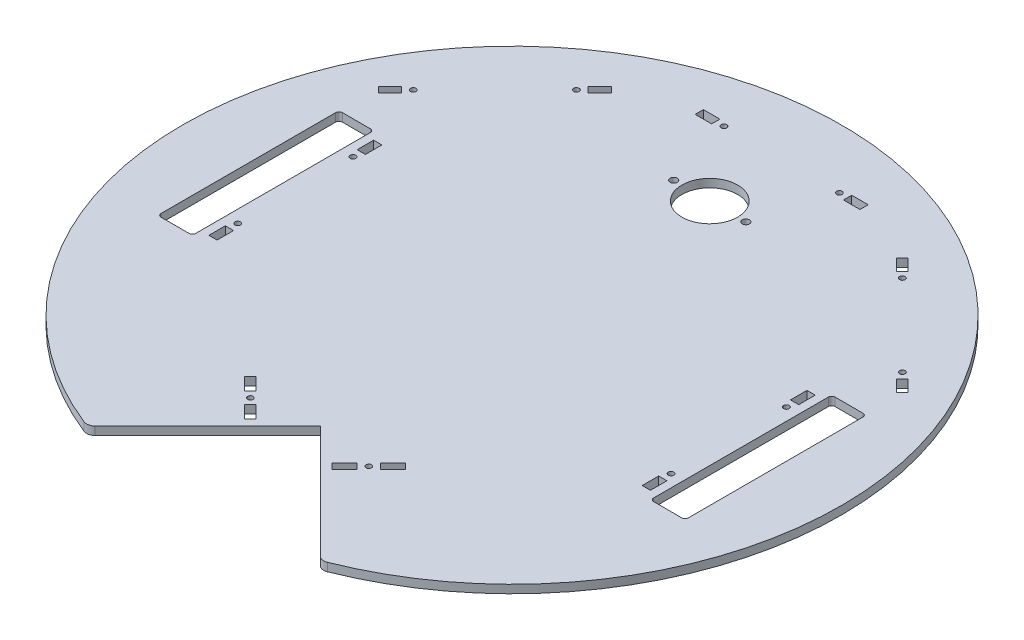
SolidWorks part; units mm, degrees
ref_plane "Front Plane" through (0, 0, 0) normal (0, 0, 1) x (1, 0, 0)
ref_plane "Top Plane" through (0, 0, 0) normal (0, 1, 0) x (1, 0, 0)
ref_plane "Right Plane" through (0, 0, 0) normal (1, 0, 0) x (0, 0, -1)
sketch "Sketch1" plane through (0, 0, 0) normal (0, 1, 0) x (1, 0, 0)
  circle A0 centre (0, 0) radius 254
  dimension "D1" = 508
extrude "Boss-Extrude1" add sketch "Sketch1" along normal blind 6.35
sketch "Sketch2" plane through (0, 6.35, 0) normal (0, 1, 0) x (1, 0, 0)
  line L0 (0, -147.7927) -> (-89.8026, -237.5952)
  line L1 (0, -36.2008) -> (0, -54.9716) construction
  line L2 (0, -147.7927) -> (89.8026, -237.5952)
  circle A0 centre (0, 0) radius 254 construction
  arc A1 (-89.8026, -237.5952) -> (89.8026, -237.5952) centre (0, 0) ccw
  dimension "D1" = 127
  dimension "D2" = 45
extrude "Cut-Extrude2" cut sketch "Sketch2" against normal through all
sketch "Sketch3" plane through (0, 6.35, 0) normal (0, 1, 0) x (1, 0, 0)
  line L0 (-31.4309, -170.2433) -> (-26.9408, -165.7532)
  line L1 (-31.4309, -170.2433) -> (-40.4112, -161.2631)
  line L2 (-26.9408, -165.7532) -> (-35.921, -156.7729)
  line L3 (-40.4112, -161.2631) -> (-35.921, -156.7729)
  line L4 (0, -147.7927) -> (-89.8026, -237.5952) construction
  line L5 (89.8026, -237.5952) -> (0, -147.7927) construction
  line L6 (-38.1661, -159.018) -> (-41.2194, -155.9647) construction
  circle A0 centre (-41.2194, -155.9647) radius 2.159
  dimension "D5" = 4.318
  dimension "D1" = 6.35
  dimension "D2" = 12.7
  dimension "D3" = 31.75
  dimension "D4" = 6.35
  dimension "D6" = 4.318
extrude "Cut-Extrude3" [suppressed] cut sketch "Sketch3" against normal through all
mirror "Mirror1" [suppressed] about plane through (0, 0, 0) normal (1, 0, 0)
sketch "Sketch4" plane through (0, 6.35, 0) normal (0, 1, 0) x (1, 0, 0)
  line L0 (0, 54.2551) -> (0, 121.7464) construction
  line L1 (-200.66, 69.85) -> (-179.07, 69.85)
  line L2 (-203.2, 67.31) -> (-203.2, -67.31)
  line L3 (-200.66, -69.85) -> (-179.07, -69.85)
  line L4 (-176.53, 67.31) -> (-176.53, -67.31)
  line L5 (-17.8666, 0) -> (24.1783, 0) construction
  line L6 (-254, -69.5481) -> (-254, -224.3367) construction
  arc A0 (-200.66, -69.85) -> (-203.2, -67.31) centre (-200.66, -67.31) cw
  arc A1 (-179.07, -69.85) -> (-176.53, -67.31) centre (-179.07, -67.31) ccw
  arc A2 (-176.53, 67.31) -> (-179.07, 69.85) centre (-179.07, 67.31) ccw
  arc A3 (-200.66, 69.85) -> (-203.2, 67.31) centre (-200.66, 67.31) ccw
  arc A4 (89.8026, -237.5952) -> (-89.8026, -237.5952) centre (0, 0) ccw construction
  dimension "D5" = 2.54
  dimension "D4" = 2.54
  dimension "D1" = 26.67
  dimension "D2" = 50.8
  dimension "D3" = 139.7
extrude "Cut-Extrude4" cut sketch "Sketch4" against normal through all
mirror "Mirror2" about plane through (0, 0, 0) normal (1, 0, 0) of "Cut-Extrude4"
sketch "Sketch6" plane through (0, 6.35, 0) normal (0, 1, 0) x (1, 0, 0)
  line L0 (-26.9408, -174.7335) -> (-85.7514, -115.9228) construction
  line L1 (0, -147.7927) -> (-89.8026, -237.5952) construction
  line L2 (89.8026, -237.5952) -> (0, -147.7927) construction
  line B0 (-47.8981, -149.286) -> (-57.6301, -139.554)
  line B1 (-47.8981, -149.286) -> (-52.3882, -153.7761)
  line B2 (-57.6301, -139.554) -> (-62.1202, -144.0441)
  line B3 (-52.3882, -153.7761) -> (-62.1202, -144.0441)
  line B4 (-38.9178, -158.2663) -> (-29.1858, -167.9983)
  line B5 (-43.408, -162.7564) -> (-33.676, -172.4884)
  line B6 (-29.1858, -167.9983) -> (-33.676, -172.4884)
  line B7 (-38.9178, -158.2663) -> (-43.408, -162.7564)
  circle B8 centre (-45.653, -156.0212) radius 2.0955
  dimension "D1" = 38.1
  dimension "D2" = 6.35
sketch_block_instance "BoltTab-1"
sketch_block "BoltTab" parameters "D1"=4.191, "D2"=6.35, "D3"=6.35
extrude "Cut-Extrude6" cut sketch "Sketch6" against normal through all
mirror "Mirror5" about plane through (0, 0, 0) normal (1, 0, 0) of "Cut-Extrude6"
sketch "Sketch8" plane through (0, 0, 0) normal (0, -1, 0) x (1, 0, 0)
  line L0 (-170.18, -63.5) -> (-170.18, -50.8) construction
  line L1 (-170.18, -63.5) -> (-163.83, -63.5) construction
  line L2 (-163.83, -63.5) -> (-163.83, -50.8) construction
  line L3 (-170.18, -50.8) -> (-163.83, -50.8) construction
  line L4 (-170.18, -63.5) -> (-170.18, -50.8)
  line L5 (-170.18, -63.5) -> (-163.83, -63.5)
  line L6 (-163.83, -63.5) -> (-163.83, -50.8)
  line L7 (-170.18, -50.8) -> (-163.83, -50.8)
  line L8 (-170.18, 50.8) -> (-163.83, 50.8) construction
  line L9 (-170.18, 63.5) -> (-170.18, 50.8) construction
  line L10 (-163.83, 63.5) -> (-163.83, 50.8) construction
  line L11 (-170.18, 63.5) -> (-163.83, 63.5) construction
  line L12 (-170.18, 50.8) -> (-163.83, 50.8)
  line L13 (-170.18, 63.5) -> (-170.18, 50.8)
  line L14 (-163.83, 63.5) -> (-163.83, 50.8)
  line L15 (-170.18, 63.5) -> (-163.83, 63.5)
  line L16 (-170.18, -46.5836) -> (-163.83, -46.5836) construction
  line L17 (-170.18, -42.3164) -> (-163.83, -42.3164) construction
  line L18 (-170.18, -46.5836) -> (-163.83, -46.5836) construction
  line L19 (-170.18, -42.3164) -> (-163.83, -42.3164) construction
  line L20 (-167.005, -42.3164) -> (-167.005, -46.5836) construction
  line L21 (-170.18, 42.3164) -> (-163.83, 42.3164) construction
  line L22 (-170.18, 46.5836) -> (-163.83, 46.5836) construction
  line L23 (-170.18, 42.3164) -> (-163.83, 42.3164) construction
  line L24 (-170.18, 46.5836) -> (-163.83, 46.5836) construction
  line L25 (-167.005, 42.3164) -> (-167.005, 46.5836) construction
  circle A0 centre (-167.005, -44.45) radius 2.1336
  circle A1 centre (-167.005, 44.45) radius 2.1336
extrude "Cut-Extrude7" cut sketch "Sketch8" against normal through all
mirror "Mirror6" about plane through (0, 0, 0) normal (1, 0, 0) of "Cut-Extrude7"
fillet "Fillet1" radius 6.35 2 edges at (89.8026, 3.175, 237.5952) (-89.8026, 3.175, 237.5952)
sketch "Sketch9" plane through (0, 0, 0) normal (0, -1, 0) x (1, 0, 0)
  line L0 (-63.5, -204.6423) -> (-63.5, -210.9923) construction
  line L1 (-63.5, -204.6423) -> (-50.8, -204.6423) construction
  line L2 (-50.8, -204.6423) -> (-50.8, -210.9923) construction
  line L3 (-63.5, -210.9923) -> (-50.8, -210.9923) construction
  line L4 (-63.5, -204.6423) -> (-63.5, -210.9923)
  line L5 (-63.5, -204.6423) -> (-50.8, -204.6423)
  line L6 (-50.8, -204.6423) -> (-50.8, -210.9923)
  line L7 (-63.5, -210.9923) -> (-50.8, -210.9923)
  line L8 (-46.5836, -204.6423) -> (-46.5836, -210.9923) construction
  line L9 (-42.3164, -204.6423) -> (-42.3164, -210.9923) construction
  line L10 (-46.5836, -204.6423) -> (-46.5836, -210.9923) construction
  line L11 (-42.3164, -204.6423) -> (-42.3164, -210.9923) construction
  line L12 (-46.5836, -207.8173) -> (-42.3164, -207.8173) construction
  line L13 (42.3164, -204.6423) -> (42.3164, -210.9923) construction
  line L14 (46.5836, -204.6423) -> (46.5836, -210.9923) construction
  line L15 (42.3164, -204.6423) -> (42.3164, -210.9923) construction
  line L16 (46.5836, -204.6423) -> (46.5836, -210.9923) construction
  line L17 (50.8, -210.9923) -> (63.5, -210.9923)
  line L18 (63.5, -210.9923) -> (63.5, -204.6423)
  line L19 (63.5, -204.6423) -> (50.8, -204.6423)
  line L20 (50.8, -204.6423) -> (50.8, -210.9923)
  line L21 (50.8, -210.9923) -> (63.5, -210.9923)
  line L22 (63.5, -210.9923) -> (63.5, -204.6423)
  line L23 (63.5, -204.6423) -> (50.8, -204.6423)
  line L24 (50.8, -204.6423) -> (50.8, -210.9923)
  line L25 (42.3164, -207.8173) -> (46.5836, -207.8173) construction
  circle A0 centre (-44.45, -207.8173) radius 2.1336
  circle A1 centre (44.45, -207.8173) radius 2.1336
  dimension "D1" = 0
extrude "Cut-Extrude8" cut sketch "Sketch9" against normal through all
sketch "Sketch10" plane through (0, 0, 0) normal (0, -1, 0) x (1, 0, 0)
  line L0 (-204.1857, -101.143) -> (-195.2055, -110.1232) construction
  line L1 (-195.2055, -110.1232) -> (-190.7153, -105.6331) construction
  line L2 (-190.7153, -105.6331) -> (-199.6956, -96.6529) construction
  line L3 (-199.6956, -96.6529) -> (-204.1857, -101.143) construction
  line L4 (-123.3634, -181.9653) -> (-114.3832, -190.9455) construction
  line L5 (-114.3832, -190.9455) -> (-109.893, -186.4554) construction
  line L6 (-109.893, -186.4554) -> (-118.8733, -177.4752) construction
  line L7 (-118.8733, -177.4752) -> (-123.3634, -181.9653) construction
  line L8 (-204.1857, -101.143) -> (-195.2055, -110.1232)
  line L9 (-195.2055, -110.1232) -> (-190.7153, -105.6331)
  line L10 (-190.7153, -105.6331) -> (-199.6956, -96.6529)
  line L11 (-199.6956, -96.6529) -> (-204.1857, -101.143)
  line L12 (-123.3634, -181.9653) -> (-114.3832, -190.9455)
  line L13 (-114.3832, -190.9455) -> (-109.893, -186.4554)
  line L14 (-109.893, -186.4554) -> (-118.8733, -177.4752)
  line L15 (-118.8733, -177.4752) -> (-123.3634, -181.9653)
  line L16 (-187.7339, -108.6146) -> (-192.224, -113.1047) construction
  line L17 (-184.7165, -111.6319) -> (-189.2067, -116.122) construction
  line L18 (-124.8721, -171.4763) -> (-129.3622, -175.9665) construction
  line L19 (-121.8547, -174.4937) -> (-126.3449, -178.9838) construction
  line L20 (-187.7339, -108.6146) -> (-192.224, -113.1047) construction
  line L21 (-184.7165, -111.6319) -> (-189.2067, -116.122) construction
  line L22 (-124.8721, -171.4763) -> (-129.3622, -175.9665) construction
  line L23 (-121.8547, -174.4937) -> (-126.3449, -178.9838) construction
  line L25 (-186.9616, -113.877) -> (-189.979, -110.8596) construction
  line L26 (-127.1172, -173.7214) -> (-124.0998, -176.7388) construction
  circle A0 centre (-188.4703, -112.3683) radius 2.1336
  circle A1 centre (-125.6085, -175.2301) radius 2.1336
extrude "Cut-Extrude9" cut sketch "Sketch10" against normal through all
mirror "Mirror7" about plane through (0, 0, 0) normal (1, 0, 0) of "Cut-Extrude9"
sketch "Sketch11" plane through (0, 6.35, 0) normal (0, 1, 0) x (1, 0, 0)
  line L0 (0, 61.4305) -> (0, 100.7164) construction
  line L1 (-82.8279, 254) -> (68.7629, 254) construction
  circle A0 centre (0, 152.4) radius 21.463
  arc A1 (93.7098, -236.0815) -> (-93.7098, -236.0815) centre (0, 0) ccw construction
  circle A2 centre (27.7813, 152.4) radius 2.7781 construction
  circle A3 centre (-27.7813, 152.4) radius 2.7781 construction
  circle A4 centre (27.7813, 152.4) radius 2.7781
  circle A5 centre (-27.7813, 152.4) radius 2.7781
  dimension "D1" = 42.926
  dimension "D2" = 101.6
extrude "Cut-Extrude10" cut sketch "Sketch11" against normal through all
